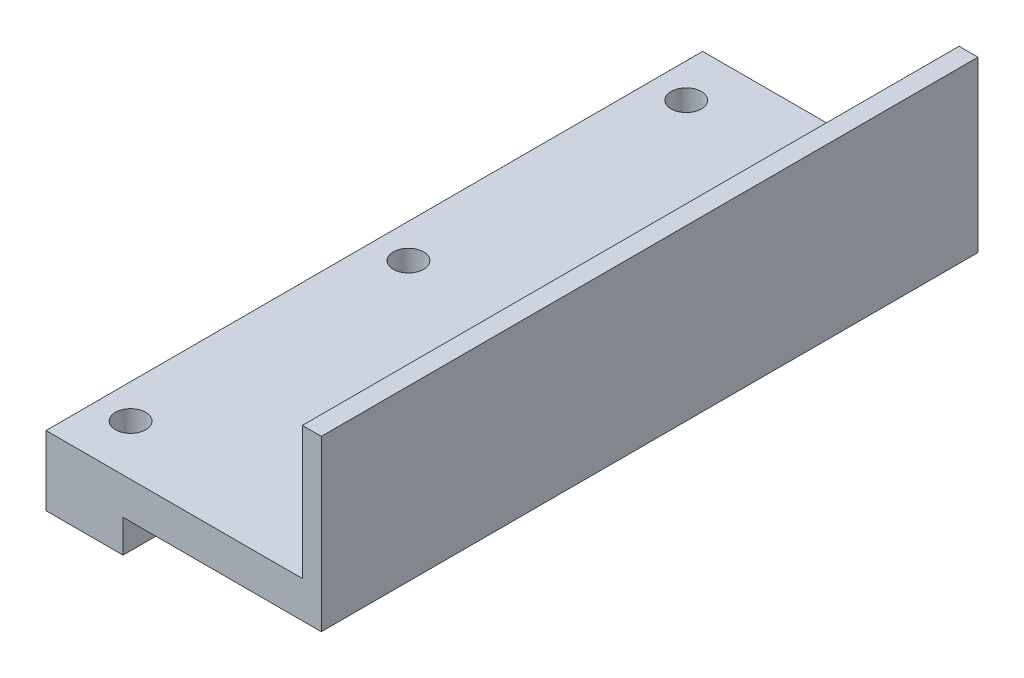
SolidWorks part; units mm, degrees
material "6061-T6 (SS)"
ref_plane "Front Plane" through (0, 0, 0) normal (0, 0, 1) x (1, 0, 0)
ref_plane "Top Plane" through (0, 0, 0) normal (0, 1, 0) x (1, 0, 0)
ref_plane "Right Plane" through (0, 0, 0) normal (1, 0, 0) x (0, 0, -1)
sketch "Sketch1" plane through (0, 0, 0) normal (0, 0, 1) x (1, 0, 0)
  line L4 (0, 0) -> (6.1, 0)
  line L17 (6.1, 2.6) -> (6.1, 0)
  line L21 (6.1, 2.6) -> (20.3, 2.6)
  line L23 (20.3, 5.5) -> (20.3, 2.6)
  line L24 (0, 0) -> (0, 5.5)
  line L25 (20.3, 5.5) -> (0, 5.5)
  dimension "D3" = 6.1
  dimension "D4" = 5.5
  dimension "D6" = 14.2
  dimension "D10" = 2.6
extrude "Boss-Extrude2" add sketch "Sketch1" along normal mid plane 52
sketch "Sketch2" plane through (0, 0, 0) normal (0, 1, 0) x (1, 0, 0)
  line L0 (20.3, 26) -> (0, 26) construction
  line L1 (0, -26) -> (0, 26) construction
  line L2 (0, 0) -> (2.7, 0) construction
  circle A0 centre (2.7, 22) radius 1.2
  circle A1 centre (2.7, 0) radius 1.2
  circle A2 centre (2.7, -22) radius 1.2
  point P9 (6.3466, 0)
  dimension "D1" = 2.4
  dimension "D2" = 2.7
  dimension "D3" = 4
  dimension "D4" = 2.7
extrude "Cut-Extrude2" cut sketch "Sketch2" against normal through all and the other way through all
sketch "Sketch3" plane through (20.3, 0, 0) normal (1, 0, 0) x (0, 0, -1)
  line L0 (-26, 2.6) -> (-26, 5.5) construction
  line L1 (26, 2.6) -> (-26, 2.6)
  line L2 (26, 2.6) -> (26, 16)
  line L3 (26, 16) -> (-26, 16)
  line L4 (-26, 2.6) -> (-26, 16)
  dimension "D1" = 13.4
extrude "Boss-Extrude3" add sketch "Sketch3" along normal blind 1.5
